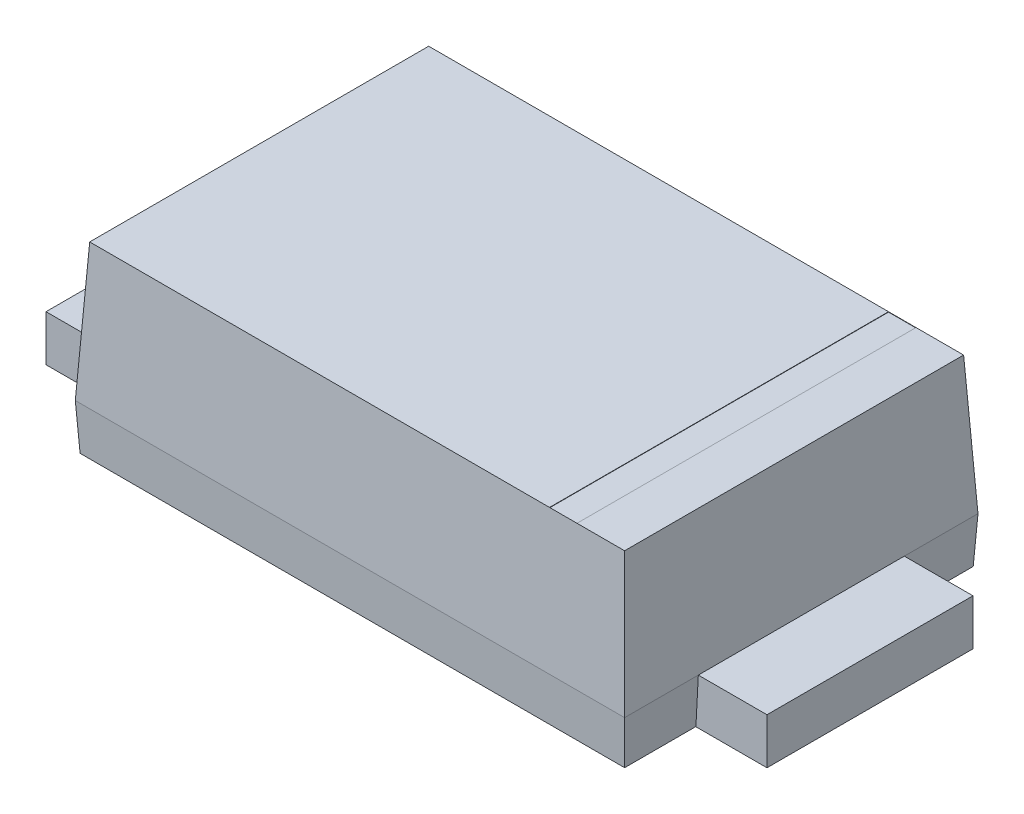
SolidWorks part; units mm, degrees
ref_plane "Front" through (0, 0, 0) normal (0, 0, 1) x (1, 0, 0)
ref_plane "Top" through (0, 0, 0) normal (0, 1, 0) x (1, 0, 0)
ref_plane "Right" through (0, 0, 0) normal (1, 0, 0) x (0, 0, -1)
ref_plane "Plane1" through (0, 0.25, 0) normal (0, 1, 0) x (1, 0, 0)
sketch "Sketch1" plane through (0, 0.25, 0) normal (0, 1, 0) x (1, 0, 0)
  line L0 (0, 0) -> (0, 23.5773) construction
  line L1 (0, 0) -> (7.5602, 0) construction
  line L2 (1.5, -0.965) -> (1.5, 0.965)
  line L3 (-1.5, -0.965) -> (-1.5, 0.965)
  line L4 (-1.5, -0.965) -> (1.5, -0.965)
  line L5 (-1.5, 0.965) -> (1.5, 0.965)
  line L6 (0, 0.965) -> (7.5602, 0.965) construction
  line L7 (0, -0.965) -> (7.5602, -0.965) construction
  line L8 (-1.5, 0) -> (-1.5, 23.5773) construction
  line L9 (1.5, 0) -> (1.5, 23.5773) construction
  dimension "D1" = 1.5
  dimension "D2" = 1.5
  dimension "D3" = 0.965
  dimension "D4" = 0.965
extrude "Boss-Extrude1" add sketch "Sketch1" along normal blind 0.75 draft 3
sketch "Sketch5" plane through (0, 0.25, 0) normal (0, -1, 0) x (1, 0, 0)
  line L4 (1.5, 0.965) -> (-1.5, 0.965)
  line L5 (-1.5, 0.965) -> (-1.5, -0.965)
  line L6 (-1.5, -0.965) -> (1.5, -0.965)
  line L7 (1.5, -0.965) -> (1.5, 0.965)
  line L8 (1.5, 0.965) -> (-1.5, 0.965)
  line L9 (-1.5, 0.965) -> (-1.5, -0.965)
  line L10 (-1.5, -0.965) -> (1.5, -0.965)
  line L11 (1.5, -0.965) -> (1.5, 0.965)
  dimension "D1" = 0
extrude "Boss-Extrude3" add sketch "Sketch5" along normal blind 0.25 draft 3
sketch "Sketch6" plane through (0, 0, 0) normal (0, -1, 0) x (1, 0, 0)
  line L0 (0, 0) -> (0, 1.1557) construction
  line L1 (0, 0) -> (1.6845, 0) construction
  line L2 (1.5, -0.965) -> (-1.5, -0.965) construction
  line L3 (-1.5, 0.965) -> (1.5, 0.965) construction
  line L4 (-1.5, -0.965) -> (-1.5, 0.965) construction
  line L5 (1.5, 0.965) -> (1.5, -0.965) construction
  line L6 (1.5, -0.965) -> (-1.5, -0.965) construction
  line L7 (-1.5, 0.965) -> (1.5, 0.965) construction
  line L8 (-1.5, -0.965) -> (-1.5, 0.965) construction
  line L9 (1.5, 0.965) -> (1.5, -0.965) construction
  line L10 (-1.375, -0.965) -> (-1.375, 0.965) construction
  line L12 (0.025, -0.625) -> (1.225, -0.625)
  line L13 (0.025, 0.625) -> (1.225, 0.625)
  line L14 (0.025, 0.625) -> (0.025, -0.625)
  line L15 (1.225, -0.5625) -> (1.225, -0.625)
  line L16 (1.225, -0.5625) -> (1.875, -0.5625)
  line L17 (1.225, 0.5625) -> (1.875, 0.5625)
  line L18 (1.875, 0.5625) -> (1.875, -0.5625)
  line L19 (0, 0.5625) -> (1.6845, 0.5625) construction
  line L20 (0, -0.5625) -> (1.6845, -0.5625) construction
  line L21 (1.225, 0.625) -> (1.225, 0.5625)
  line L23 (-2, -0.625) -> (-2, 0.625)
  line L25 (-2, 0.625) -> (-1.225, 0.625)
  line L27 (-1.225, -0.625) -> (-2, -0.625)
  line L28 (-1.225, -0.625) -> (-1.225, 0.625)
  line L29 (-2, -0.965) -> (-2, 0.965) construction
  line L30 (1.225, 0.965) -> (1.225, -0.965) construction
  line L31 (-1.225, -0.965) -> (-1.225, 0.965) construction
  point P10 (1.375, 0.965)
  point P11 (1.375, -0.965)
  point P13 (1.6845, -0.625)
  point P15 (1.6845, 0.625)
  dimension "D3" = 0.625
  dimension "D9" = 1.25
  dimension "D10" = 1.125
  dimension "D13" = 0.625
  dimension "D1" = 0.125
  dimension "D4" = 0.5625
  dimension "D6" = 0.5625
  dimension "D8" = 0.5
  dimension "D11" = 0.275
  dimension "D12" = 0.275
extrude "Boss-Extrude4" add sketch "Sketch6" against normal blind 0.25 and the other way blind 0.001
sketch "Sketch7" plane through (0, 1, 0) normal (0, 1, 0) x (1, 0, 0)
  line L0 (1.0507, -0.9257) -> (1.0507, 0.9257)
  line L1 (-1.4607, -0.9257) -> (1.4607, -0.9257) construction
  line L2 (1.4607, 0.9257) -> (-1.4607, 0.9257) construction
  line L3 (1.0507, 0.9257) -> (1.2007, 0.9257)
  line L4 (1.2007, 0.9257) -> (1.2007, -0.9257)
  line L5 (1.2007, -0.9257) -> (1.0507, -0.9257)
  line L6 (1.4607, -0.9257) -> (1.4607, 0.9257) construction
  point P9 (0, 0)
  dimension "D1" = 0.15
  dimension "D2" = 0.26
extrude "Cut-Extrude1" cut sketch "Sketch7" against normal blind 0.002
